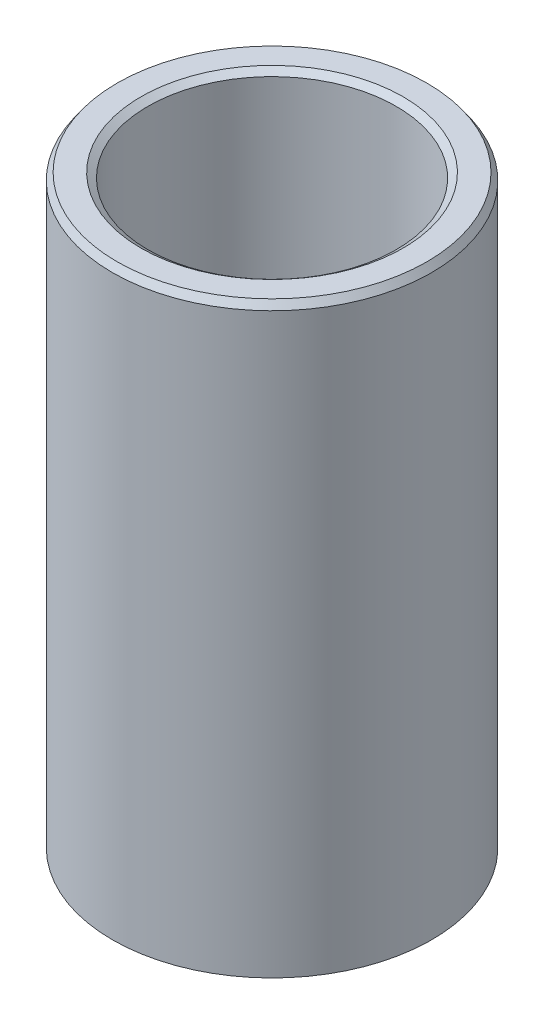
SolidWorks part; units mm, degrees
ref_plane "Front Plane" through (0, 0, 0) normal (0, 0, 1) x (1, 0, 0)
ref_plane "Top Plane" through (0, 0, 0) normal (0, 1, 0) x (1, 0, 0)
ref_plane "Right Plane" through (0, 0, 0) normal (1, 0, 0) x (0, 0, -1)
sketch "Sketch1" plane through (0, 0, 0) normal (0, 1, 0) x (1, 0, 0)
  circle A0 centre (0, 0) radius 37.5
  dimension "SLEEVE_OD" = 75
extrude "Boss-Extrude1" add sketch "Sketch1" along normal blind 138.4748
sketch "Sketch2" plane through (0, 0, 0) normal (0, 1, 0) x (1, 0, 0)
  circle A0 centre (0, 0) radius 29.1684
  dimension "BORE_D" = 58.3368
extrude "Cut-Extrude1" cut sketch "Sketch2" along normal through all
chamfer "Chamfer1" distance 1.6283 angle 34.821 4 edges at (0, 138.4748, 29.1684) (0, 0, 29.1684) (0, 0, 37.5) (0, 138.4748, 37.5) first distance on face at (0, 138.4748, 29.1684) first distance on face at (0, 0, 29.1684) first distance on face at (0, 138.4748, 37.5)
